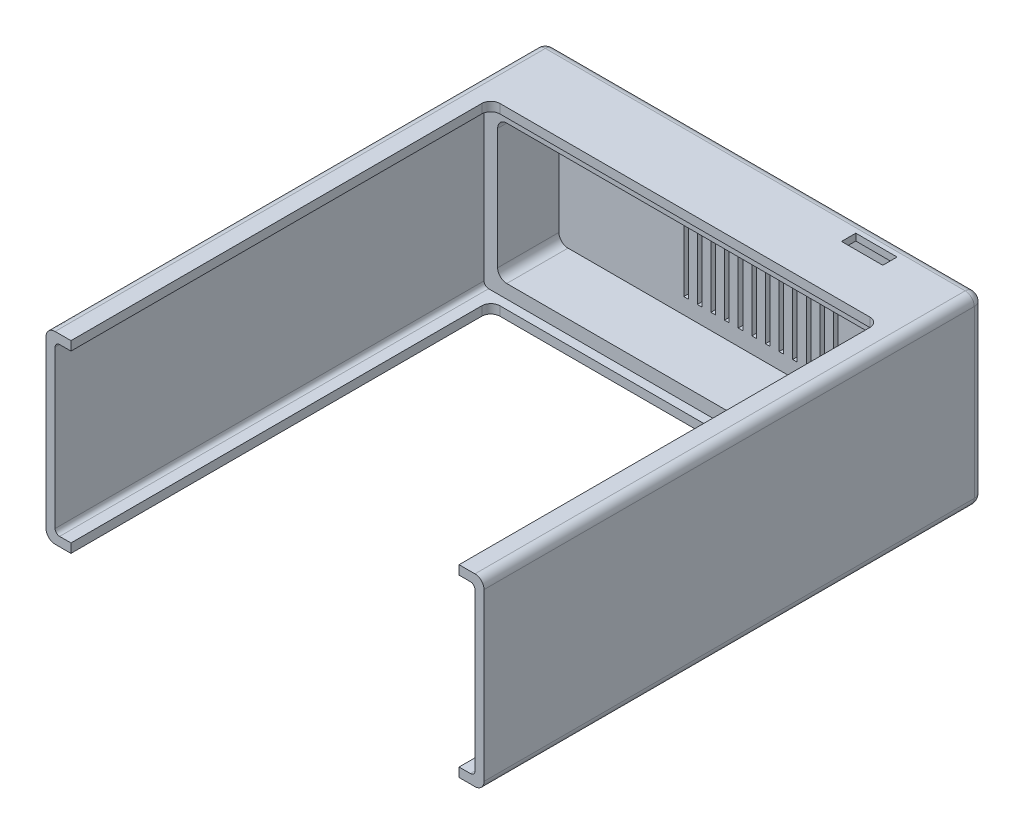
SolidWorks part; units mm, degrees
ref_plane "Ön Düzlem" through (0, 0, 0) normal (0, 0, 1) x (1, 0, 0)
ref_plane "Üst Düzlem" through (0, 0, 0) normal (0, 1, 0) x (1, 0, 0)
ref_plane "Sağ Düzlem" through (0, 0, 0) normal (1, 0, 0) x (0, 0, -1)
sketch "Çizim1" plane through (0, 0, 0) normal (0, 0, 1) x (1, 0, 0)
  line L1 (-48.25, -20.3) -> (48.25, -20.3)
  line L2 (-48.25, -20.3) -> (-48.25, 20.3)
  line L3 (-48.25, 20.3) -> (48.25, 20.3)
  line L4 (48.25, -20.3) -> (48.25, 20.3)
  line L5 (-48.25, -20.3) -> (48.25, 20.3) construction
  line L6 (-48.25, 20.3) -> (48.25, -20.3) construction
  point P0 (0, 0)
  dimension "D1" = 96.5
  dimension "D2" = 40.6
extrude "Yükseklik-Ekstrüzyon1" add sketch "Çizim1" along normal blind 110
sketch "Çizim2" plane through (0, 0, 110) normal (0, 0, 1) x (1, 0, 0)
  line L0 (-48.25, 20.3) -> (-48.25, -20.3) construction
  line L1 (-46.25, -18.3) -> (-42.75, -18.3)
  line L2 (-46.25, -18.3) -> (-46.25, 18.3)
  line L3 (-46.25, 18.3) -> (-42.75, 18.3)
  line L4 (46.25, -18.3) -> (46.25, 18.3)
  line L5 (-46.25, -18.3) -> (46.25, 18.3) construction
  line L6 (-46.25, 18.3) -> (46.25, -18.3) construction
  line L7 (-48.25, -20.3) -> (48.25, -20.3) construction
  line L8 (-42.75, -18.3) -> (-42.75, -20.3)
  line L9 (-42.75, -20.3) -> (42.75, -20.3)
  line L10 (42.75, -20.3) -> (42.75, -18.3)
  line L11 (42.75, 18.3) -> (42.75, 20.3)
  line L12 (48.25, 20.3) -> (-48.25, 20.3) construction
  line L13 (42.75, 20.3) -> (-42.75, 20.3)
  line L14 (-42.75, 20.3) -> (-42.75, 18.3)
  line L15 (42.75, -18.3) -> (46.25, -18.3)
  line L16 (42.75, 18.3) -> (46.25, 18.3)
  point P0 (0, 0)
  point P18 (-42.75, 19.3)
  point P21 (0, 0)
  point P22 (0, 0)
  dimension "D1" = 2
  dimension "D2" = 2
  dimension "D3" = 3.5
  dimension "D4" = 3.5
extrude "Kes-Ekstrüzyon1" cut sketch "Çizim2" against normal blind 92.5
sketch "Çizim3" plane through (0, 0, 17.5) normal (0, 0, 1) x (1, 0, 0)
  line L1 (-46.25, -18.3) -> (46.25, -18.3)
  line L2 (-46.25, -18.3) -> (-46.25, 18.3)
  line L3 (-46.25, 18.3) -> (46.25, 18.3)
  line L4 (46.25, -18.3) -> (46.25, 18.3)
  line L5 (-46.25, -18.3) -> (46.25, 18.3) construction
  line L6 (-46.25, 18.3) -> (46.25, -18.3) construction
  point P0 (0, 0)
extrude "Kes-Ekstrüzyon2" cut sketch "Çizim3" against normal blind 2
sketch "Çizim4" plane through (0, 0, 15.5) normal (0, 0, 1) x (1, 0, 0)
  line L0 (-46.25, 18.3) -> (-46.25, -18.3) construction
  line L1 (-43.25, -15.3) -> (43.25, -15.3)
  line L2 (-43.25, -15.3) -> (-43.25, 15.3)
  line L3 (-43.25, 15.3) -> (43.25, 15.3)
  line L4 (43.25, -15.3) -> (43.25, 15.3)
  line L5 (-43.25, -15.3) -> (43.25, 15.3) construction
  line L6 (-43.25, 15.3) -> (43.25, -15.3) construction
  line L7 (46.25, 18.3) -> (-46.25, 18.3) construction
  point P0 (0, 0)
  dimension "D1" = 3
  dimension "D2" = 3
extrude "Kes-Ekstrüzyon3" cut sketch "Çizim4" against normal blind 13.5
fillet "Radyus1" radius 2 16 edges at (-48.25, 0, 0) (48.25, 0, 0) (0, -20.3, 0) (0, 20.3, 0) (48.25, 20.3, 55) (-48.25, -20.3, 55) (48.25, -20.3, 55) (-48.25, 20.3, 55) (43.25, 15.3, 8.75) (-43.25, 15.3, 8.75) (-43.25, -15.3, 8.75) (43.25, -15.3, 8.75) (-42.75, 19.3, 17.5) (-42.75, -19.3, 17.5) (42.75, -19.3, 17.5) (42.75, 19.3, 17.5)
fillet "Radyus2" radius 1 4 edges at (46.25, -18.3, 62.75) (-46.25, -18.3, 62.75) (-46.25, 18.3, 62.75) (46.25, 18.3, 62.75)
sketch "Çizim5" plane through (0, 15.3, 0) normal (0, -1, 0) x (1, 0, 0)
  line L0 (-46.25, 2) -> (46.25, 2) construction
  line L1 (17.75, 2) -> (37.75, 2)
  line L2 (17.75, 2) -> (17.75, 7)
  line L3 (17.75, 7) -> (37.75, 7)
  line L4 (37.75, 2) -> (37.75, 7)
  line L5 (42.75, 19.5) -> (42.75, 110) construction
  dimension "D1" = 20
  dimension "D2" = 5
  dimension "D3" = 5
extrude "Kes-Ekstrüzyon4" cut sketch "Çizim5" against normal blind 3.5
chamfer "Pah3" distance 8.5 distance2 5 1 edges at (27.75, 15.3, 7)
sketch "Çizim6" plane through (0, 18.8, 0) normal (0, -1, 0) x (1, 0, 0)
  line L0 (46.25, 2) -> (-46.25, 2) construction
  line L1 (23.2, 6.2) -> (32.3, 6.2)
  line L2 (23.2, 6.2) -> (23.2, 3.05)
  line L3 (23.2, 3.05) -> (32.3, 3.05)
  line L4 (32.3, 6.2) -> (32.3, 3.05)
  line L5 (37.75, 9.55) -> (17.75, 9.55) construction
  point P8 (27.75, 9.55)
  point P9 (27.75, 3.05)
  dimension "D1" = 9.1
  dimension "D2" = 3.15
  dimension "D3" = 1.05
extrude "Kes-Ekstrüzyon5" cut sketch "Çizim6" against normal blind 1.5
sketch "Çizim7" plane through (0, 0, 2) normal (0, 0, 1) x (1, 0, 0)
  line L0 (18.25, 11.8) -> (18.25, -11.8)
  line L1 (18.25, -11.8) -> (17.25, -11.8)
  line L2 (17.25, -11.8) -> (17.25, 11.8)
  line L3 (17.25, 11.8) -> (18.25, 11.8)
  line L4 (43.25, -13.3) -> (43.25, 13.3) construction
  line L5 (-41.25, -15.3) -> (41.25, -15.3) construction
  line L7 (43.25, -13.3) -> (43.25, 13.3) construction
  line L8 (14.25, 11.8) -> (15.25, 11.8)
  line L9 (15.25, 11.8) -> (15.25, -11.8)
  line L10 (15.25, -11.8) -> (14.25, -11.8)
  line L11 (14.25, -11.8) -> (14.25, 11.8)
  line L12 (11.25, 11.8) -> (12.25, 11.8)
  line L13 (12.25, 11.8) -> (12.25, -11.8)
  line L14 (12.25, -11.8) -> (11.25, -11.8)
  line L15 (11.25, -11.8) -> (11.25, 11.8)
  line L16 (8.25, 11.8) -> (9.25, 11.8)
  line L17 (9.25, 11.8) -> (9.25, -11.8)
  line L18 (9.25, -11.8) -> (8.25, -11.8)
  line L19 (8.25, -11.8) -> (8.25, 11.8)
  line L20 (5.25, 11.8) -> (6.25, 11.8)
  line L21 (6.25, 11.8) -> (6.25, -11.8)
  line L22 (6.25, -11.8) -> (5.25, -11.8)
  line L23 (5.25, -11.8) -> (5.25, 11.8)
  line L24 (2.25, 11.8) -> (3.25, 11.8)
  line L25 (3.25, 11.8) -> (3.25, -11.8)
  line L26 (3.25, -11.8) -> (2.25, -11.8)
  line L27 (2.25, -11.8) -> (2.25, 11.8)
  line L28 (-0.75, 11.8) -> (0.25, 11.8)
  line L29 (0.25, 11.8) -> (0.25, -11.8)
  line L30 (0.25, -11.8) -> (-0.75, -11.8)
  line L31 (-0.75, -11.8) -> (-0.75, 11.8)
  line L32 (-3.75, 11.8) -> (-2.75, 11.8)
  line L33 (-2.75, 11.8) -> (-2.75, -11.8)
  line L34 (-2.75, -11.8) -> (-3.75, -11.8)
  line L35 (-3.75, -11.8) -> (-3.75, 11.8)
  line L36 (-6.75, 11.8) -> (-5.75, 11.8)
  line L37 (-5.75, 11.8) -> (-5.75, -11.8)
  line L38 (-5.75, -11.8) -> (-6.75, -11.8)
  line L39 (-6.75, -11.8) -> (-6.75, 11.8)
  line L40 (-9.75, 11.8) -> (-8.75, 11.8)
  line L41 (-8.75, 11.8) -> (-8.75, -11.8)
  line L42 (-8.75, -11.8) -> (-9.75, -11.8)
  line L43 (-9.75, -11.8) -> (-9.75, 11.8)
  line L44 (-12.75, 11.8) -> (-11.75, 11.8)
  line L45 (-11.75, 11.8) -> (-11.75, -11.8)
  line L46 (-11.75, -11.8) -> (-12.75, -11.8)
  line L47 (-12.75, -11.8) -> (-12.75, 11.8)
  line L48 (-15.75, 11.8) -> (-14.75, 11.8)
  line L49 (-14.75, 11.8) -> (-14.75, -11.8)
  line L50 (-14.75, -11.8) -> (-15.75, -11.8)
  line L51 (-15.75, -11.8) -> (-15.75, 11.8)
  point P6 (43.25, 0)
  point P7 (18.25, 0)
  dimension "D1" = 1
  dimension "D2" = 3.5
  dimension "D3" = 25
  dimension "D5" = 2
  dimension "D4" = 12
extrude "Kes-Ekstrüzyon6" cut sketch "Çizim7" against normal blind 2
